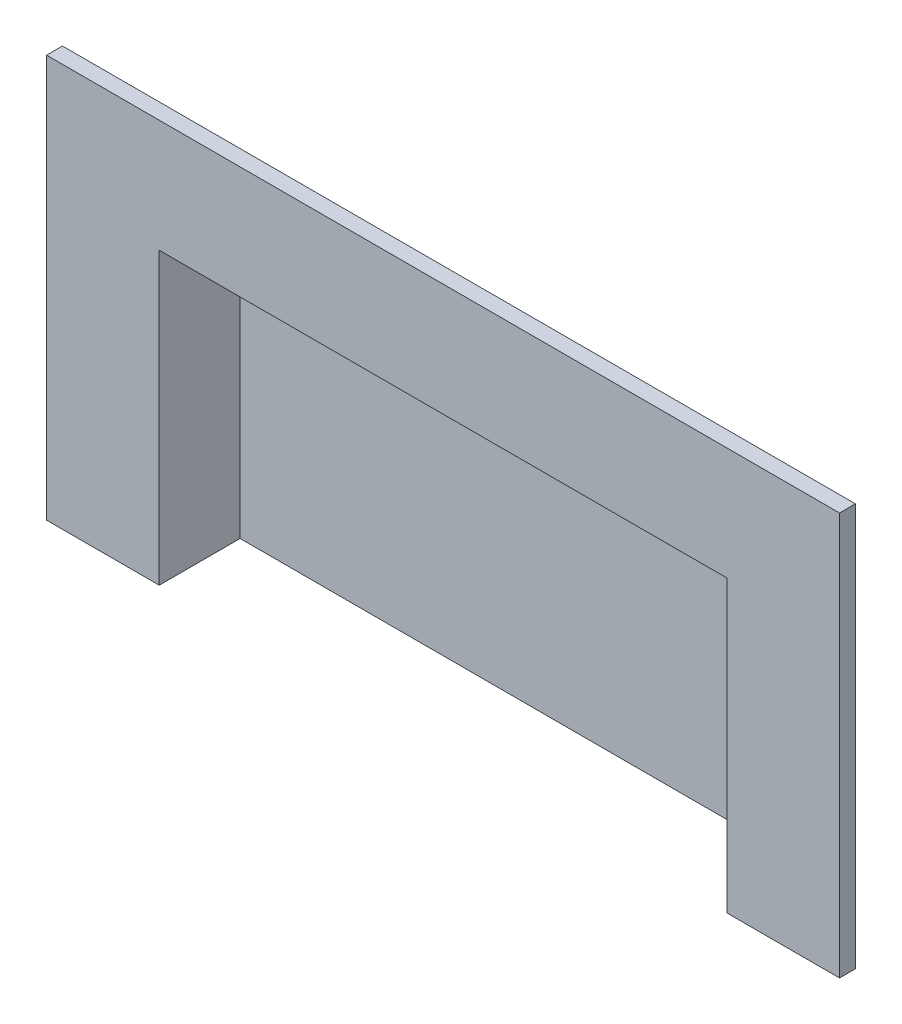
SolidWorks part; units mm, degrees
material "6063-O"
ref_plane "Front Plane" through (0, 0, 0) normal (0, 0, 1) x (1, 0, 0)
ref_plane "Top Plane" through (0, 0, 0) normal (0, 1, 0) x (1, 0, 0)
ref_plane "Right Plane" through (0, 0, 0) normal (1, 0, 0) x (0, 0, -1)
sketch "Sketch1" plane through (0, 0, 0) normal (0, 0, 1) x (1, 0, 0)
  line L1 (-48, -24.5) -> (48, -24.5)
  line L2 (-48, -24.5) -> (-48, 24.5)
  line L3 (-48, 24.5) -> (48, 24.5)
  line L4 (48, -24.5) -> (48, 24.5)
  line L5 (-48, -24.5) -> (48, 24.5) construction
  line L6 (-48, 24.5) -> (48, -24.5) construction
  point P0 (0, 0)
  dimension "D1" = 49
  dimension "D2" = 96
extrude "Boss-Extrude1" add sketch "Sketch1" along normal blind 15.494
sketch "Sketch2" plane through (0, 0, 15.494) normal (0, 0, 1) x (1, 0, 0)
  line L0 (-48, -24.5) -> (48, -24.5) construction
  line L1 (-63.5, -24.5) -> (63.5, -24.5)
  line L2 (-63.5, -24.5) -> (-63.5, 40)
  line L3 (-63.5, 40) -> (63.5, 40)
  line L4 (63.5, -24.5) -> (63.5, 40)
  line L9 (48, 24.5) -> (-48, 24.5) construction
  point P6 (0, 40)
  dimension "D1" = 127
  dimension "D2" = 15.5
extrude "Boss-Extrude2" add sketch "Sketch2" against normal blind 2.54
shell "Shell1" thickness 2.54 removed face at (0, -24.5, 10.3505) removed face at (0, 7.75, 15.494)
